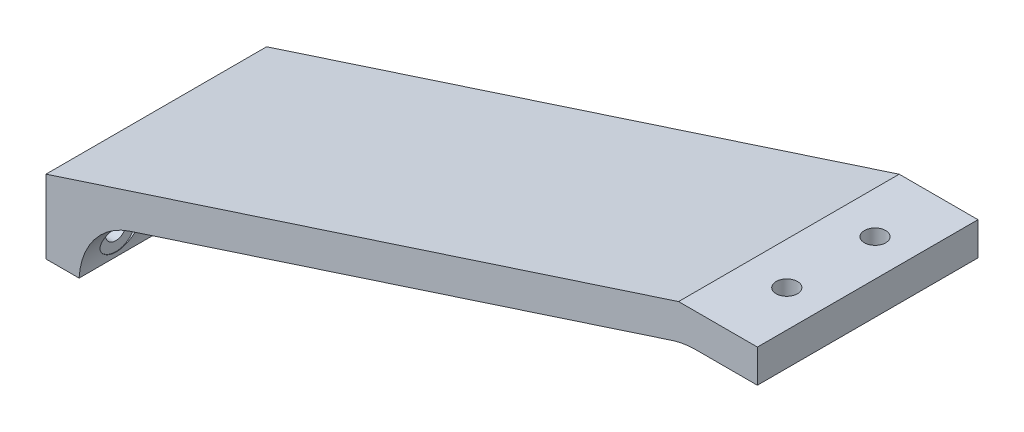
SolidWorks part; units mm, degrees
material "Onyx w/ CF"
ref_plane "Front Plane" through (0, 0, 0) normal (0, 0, 1) x (1, 0, 0)
ref_plane "Top Plane" through (0, 0, 0) normal (0, 1, 0) x (1, 0, 0)
ref_plane "Right Plane" through (0, 0, 0) normal (1, 0, 0) x (0, 0, -1)
sketch "Sketch1" plane through (0, 0, 0) normal (0, 0, 1) x (1, 0, 0)
  line L0 (0, 0) -> (0, -10)
  line L1 (0, -10) -> (4.5, -10)
  line L2 (4.5, -10) -> (4.5, -3.2676)
  line L3 (4.5, -3.2676) -> (86.73, 23.5)
  line L4 (86.73, 23.5) -> (96.73, 23.5)
  line L5 (96.73, 23.5) -> (96.73, 28)
  line L6 (96.73, 28) -> (86.016, 28)
  line L7 (86.016, 28) -> (0, 0)
  dimension "D1" = 4.5
  dimension "D2" = 4.5
  dimension "D3" = 10
  dimension "D4" = 96.73
  dimension "D5" = 10
  dimension "D6" = 38
extrude "Boss-Extrude1" add sketch "Sketch1" along normal mid plane 30
hole_wizard "M2.5 Clearance Hole1" positions "Sketch2" profile "Sketch3" hole size "M2.5" standard "ANSI Metric" end condition through all
sketch "Sketch2" plane through (0, 23.5, 0) normal (0, -1, 0) x (-1, 0, 0)
  line L0 (-91.73, -6) -> (-91.73, 6)
  line L2 (-96.73, -15) -> (-96.73, 15) construction
  line L3 (-86.73, -15) -> (-96.73, -15) construction
  point P0 (-91.73, -6)
  point P2 (-91.73, 6)
  point P12 (-96.73, 0)
  point P13 (-91.73, 0)
  point P17 (-91.73, -15)
  dimension "D1" = 12
sketch "Sketch3" plane through (91.73, 23.5, 6) normal (1, 0, 0) x (0, 0, -1)
  line L0 (0, 0) -> (0, 4.5)
  line L1 (0, 4.5) -> (1.45, 4.5)
  line L2 (1.45, 4.5) -> (1.45, 0)
  line L5 (1.45, 0) -> (0, 0)
  line L11 (0, -6.35) -> (0, 107.95) construction
  dimension "Thru Hole Dia." = 2.9
  dimension "Thru Hole Depth" = 4.5
hole_wizard "M2.5 Clearance Hole2" positions "Sketch4" profile "Sketch5" hole size "M2.5" standard "ANSI Metric" end condition through all
sketch "Sketch4" plane through (4.5, 0, 0) normal (1, 0, 0) x (0, 0, -1)
  line L0 (-10, -6.6338) -> (10, -6.6338)
  line L2 (-15, -3.2676) -> (15, -3.2676) construction
  line L3 (-15, -10) -> (-15, -3.2676) construction
  point P0 (-10, -6.6338)
  point P2 (10, -6.6338)
  point P10 (0, -3.2676)
  point P11 (0, -6.6338)
  point P15 (-15, -6.6338)
  dimension "D1" = 20
sketch "Sketch5" plane through (4.5, -6.6338, 10) normal (0, 1, 0) x (0, 0, -1)
  line L0 (0, 0) -> (0, 4.5)
  line L1 (0, 4.5) -> (1.45, 4.5)
  line L2 (1.45, 4.5) -> (1.45, 0)
  line L5 (1.45, 0) -> (0, 0)
  line L11 (0, -6.35) -> (0, 107.95) construction
  dimension "Thru Hole Dia." = 2.9
  dimension "Thru Hole Depth" = 4.5
fillet "Fillet1" radius 10 2 edges at (86.73, 23.5, 0) (4.5, -3.2676, 0)
sketch "Sketch6" plane through (0, 0, 0) normal (-1, 0, 0) x (0, 0, 1)
  line L0 (-10, -6.6338) -> (10, -6.6338) construction
  line L1 (15, -10) -> (-15, -10) construction
  circle A0 centre (-10, -6.6338) radius 2.75
  circle A1 centre (10, -6.6338) radius 2.75
  point P4 (0, -6.6338)
  dimension "D1" = 5.5
  dimension "D2" = 20
  dimension "D3" = 3.3662
extrude "Cut-Extrude1" cut sketch "Sketch6" against normal blind 10 from vertex starting at point (4.5, -10, 15)
